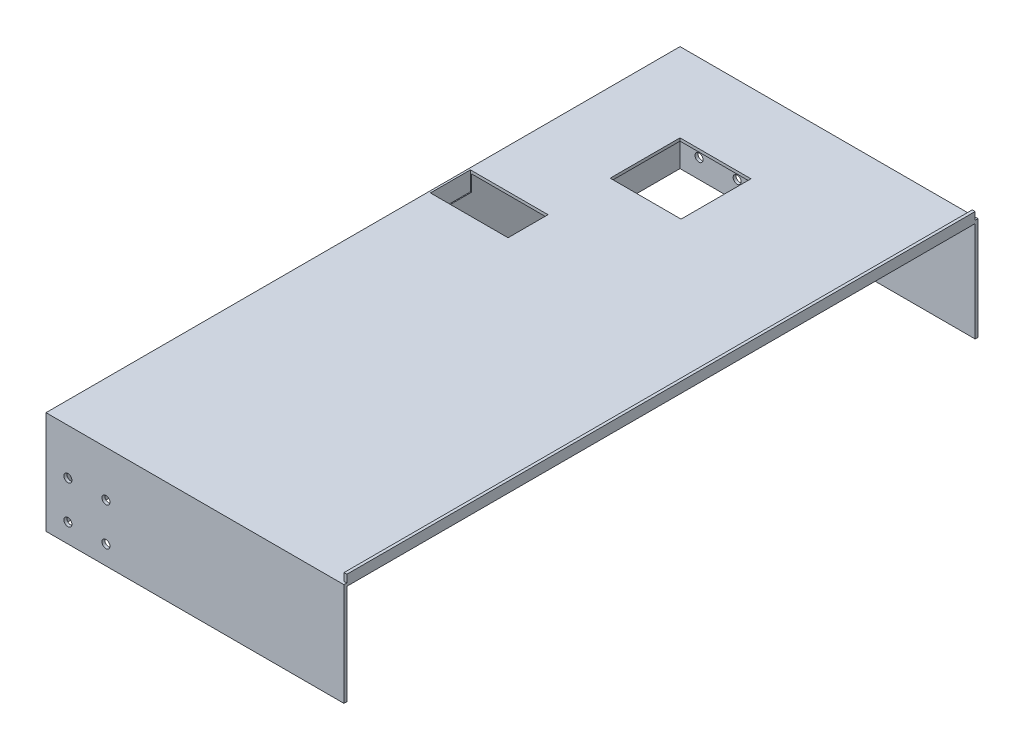
SolidWorks part; units mm, degrees
ref_plane "Front Plane" through (0, 0, 0) normal (0, 0, 1) x (1, 0, 0)
ref_plane "Top Plane" through (0, 0, 0) normal (0, 1, 0) x (1, 0, 0)
ref_plane "Right Plane" through (0, 0, 0) normal (1, 0, 0) x (0, 0, -1)
sketch "Sketch4" plane through (0, 0, 0) normal (0, 1, 0) x (1, 0, 0)
  line L0 (179.4784, 330) -> (334.4784, 330)
  line L1 (334.4784, 330) -> (334.4784, 0)
  line L2 (334.4784, 0) -> (179.4784, 0)
  line L3 (179.4784, 0) -> (179.4784, 200)
  line L7 (179.4784, 265) -> (179.4784, 330)
  line L8 (179.4784, 200) -> (179.4784, 265)
  dimension "D2" = 65
  dimension "D4" = 200
  dimension "D5" = 155
  dimension "D6" = 155
extrude "Boss-Extrude4" add sketch "Sketch4" along normal blind 1.5 separate body
sketch "Sketch5" plane through (0, 0, 0) normal (0, 0, 1) x (1, 0, 0)
  line L1 (179.4784, 1.5) -> (334.4784, 1.5)
  line L2 (179.4784, 1.5) -> (179.4784, -52.5)
  line L3 (179.4784, -52.5) -> (334.4784, -52.5)
  line L4 (334.4784, 1.5) -> (334.4784, -52.5)
  dimension "D1" = 54
sketch "Sketch7" plane through (0, 0, -330) normal (0, 0, -1) x (-1, 0, 0)
  line L1 (-179.4784, 1.5) -> (-334.4784, 1.5)
  line L2 (-179.4784, 1.5) -> (-179.4784, -52.5)
  line L3 (-179.4784, -52.5) -> (-334.4784, -52.5)
  line L4 (-334.4784, 1.5) -> (-334.4784, -52.5)
  dimension "D1" = 54
  dimension "D2" = 155
sketch "Sketch8" plane through (0, 1.5, 0) normal (0, 1, 0) x (1, 0, 0)
  line L0 (179.4784, 330) -> (334.4784, 330) construction
  line L1 (334.4784, 0) -> (332.9784, 0)
  line L2 (334.4784, 0) -> (334.4784, 330)
  line L3 (334.4784, 330) -> (332.9784, 330)
  line L4 (332.9784, 0) -> (332.9784, 330)
  dimension "D1" = 1.5
extrude "Boss-Extrude5" add sketch "Sketch5" along normal blind 1.5
extrude "Boss-Extrude14" add sketch "Sketch8" along normal blind 4
extrude "Boss-Extrude18" add sketch "Sketch7" along normal blind 1.5
sketch "Sketch9" plane through (179.4784, 0, 0) normal (-1, 0, 0) x (0, 0, 1)
  line L1 (-331.5, 1.5) -> (1.5, 1.5)
  line L2 (-331.5, 1.5) -> (-331.5, -52.5)
  line L3 (-331.5, -52.5) -> (1.5, -52.5)
  line L4 (1.5, 1.5) -> (1.5, -52.5)
extrude "Boss-Extrude19" add sketch "Sketch9" along normal blind 1.5
sketch "Sketch10" plane through (0, 0, -331.5) normal (0, 0, -1) x (-1, 0, 0)
  circle A0 centre (-209.4784, -42.5) radius 2.1
sketch "Sketch11" plane through (0, 0, -331.5) normal (0, 0, -1) x (-1, 0, 0)
  circle A0 centre (-189.4784, -42.5) radius 2.1
sketch "Sketch12" plane through (0, 0, -331.5) normal (0, 0, -1) x (-1, 0, 0)
  circle A0 centre (-189.4784, -22.5) radius 2.1
sketch "Sketch13" plane through (0, 0, -331.5) normal (0, 0, -1) x (-1, 0, 0)
  circle A0 centre (-209.4784, -22.5) radius 2.1
sketch "Sketch14" plane through (0, 0, 1.5) normal (0, 0, 1) x (1, 0, 0)
  circle A0 centre (189.4784, -22.5) radius 2.1
sketch "Sketch15" plane through (0, 0, 1.5) normal (0, 0, 1) x (1, 0, 0)
  circle A0 centre (209.4784, -22.5) radius 2.1
sketch "Sketch16" plane through (0, 0, 1.5) normal (0, 0, 1) x (1, 0, 0)
  circle A0 centre (189.4784, -42.5) radius 2.1
sketch "Sketch17" plane through (0, 0, 1.5) normal (0, 0, 1) x (1, 0, 0)
  circle A0 centre (209.4784, -42.5) radius 2.1
extrude "Cut-Extrude1" cut sketch "Sketch10" against normal blind 10
extrude "Cut-Extrude2" cut sketch "Sketch17" against normal blind 10
extrude "Cut-Extrude3" cut sketch "Sketch16" against normal blind 10
extrude "Cut-Extrude4" cut sketch "Sketch11" against normal blind 10
extrude "Cut-Extrude5" cut sketch "Sketch12" against normal blind 10
extrude "Cut-Extrude6" cut sketch "Sketch13" against normal blind 10
extrude "Cut-Extrude7" cut sketch "Sketch14" against normal blind 10
extrude "Cut-Extrude8" cut sketch "Sketch15" against normal blind 10
sketch "Sketch18" plane through (0, 1.5, 0) normal (0, 1, 0) x (1, 0, 0)
  line L1 (178.9875, 220.3848) -> (219.7642, 220.3848)
  line L2 (178.9875, 220.3848) -> (178.9875, 199.3811)
  line L3 (178.9875, 199.3811) -> (219.7642, 199.3811)
  line L4 (219.7642, 220.3848) -> (219.7642, 199.3811)
extrude "Cut-Extrude9" cut sketch "Sketch18" against normal blind 10
sketch "Sketch21" plane through (0, 1.5, 0) normal (0, 1, 0) x (1, 0, 0)
  line L1 (219.4784, 290) -> (256.7252, 290)
  line L2 (219.4784, 290) -> (219.4784, 253.3051)
  line L3 (219.4784, 253.3051) -> (256.7252, 253.3051)
  line L4 (256.7252, 290) -> (256.7252, 253.3051)
extrude "Cut-Extrude12" cut sketch "Sketch21" against normal blind 10
